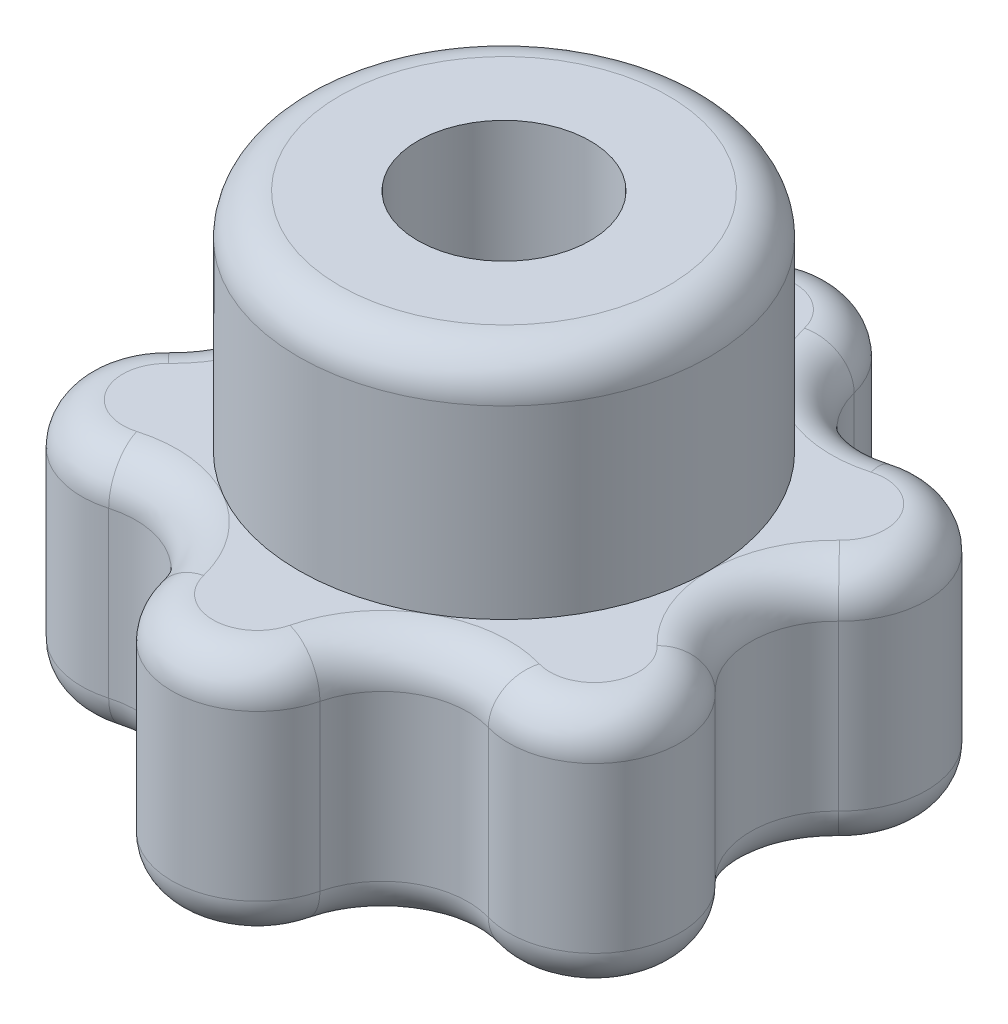
SolidWorks part; units mm, degrees
ref_plane "Спереди" through (0, 0, 0) normal (0, 0, 1) x (1, 0, 0)
ref_plane "Сверху" through (0, 0, 0) normal (0, 1, 0) x (1, 0, 0)
ref_plane "Справа" through (0, 0, 0) normal (1, 0, 0) x (0, 0, -1)
sketch "Эскиз1" plane through (0, 0, 0) normal (0, 1, 0) x (1, 0, 0)
  line L1 (0, 4.2147) -> (-3.65, 2.1073)
  line L2 (-3.65, 2.1073) -> (-3.65, -2.1073)
  line L3 (-3.65, -2.1073) -> (0, -4.2147)
  line L4 (0, -4.2147) -> (3.65, -2.1073)
  line L5 (3.65, -2.1073) -> (3.65, 2.1073)
  line L6 (3.65, 2.1073) -> (0, 4.2147)
  circle A0 centre (0, 0) radius 6 construction
  arc A1 (2.0203, 6.4992) -> (-2.0203, 6.4992) centre (0, 6) ccw
  arc A2 (2.0203, 6.4992) -> (4.6183, 4.9992) centre (4.0405, 6.9984) ccw
  arc A3 (-2.0203, -6.4992) -> (2.0203, -6.4992) centre (0, -6) ccw
  arc A4 (4.6183, -4.9992) -> (2.0203, -6.4992) centre (4.0405, -6.9984) ccw
  arc A5 (6.6386, 1.5) -> (4.6183, 4.9992) centre (5.1962, 3) ccw
  arc A6 (6.6386, 1.5) -> (6.6386, -1.5) centre (8.081, 0) ccw
  arc A7 (4.6183, -4.9992) -> (6.6386, -1.5) centre (5.1962, -3) ccw
  arc A8 (-4.6183, 4.9992) -> (-2.0203, 6.4992) centre (-4.0405, 6.9984) ccw
  arc A9 (-4.6183, 4.9992) -> (-6.6386, 1.5) centre (-5.1962, 3) ccw
  arc A10 (-6.6386, -1.5) -> (-6.6386, 1.5) centre (-8.081, 0) ccw
  arc A11 (-2.0203, -6.4992) -> (-4.6183, -4.9992) centre (-4.0405, -6.9984) ccw
  arc A12 (-6.6386, -1.5) -> (-4.6183, -4.9992) centre (-5.1962, -3) ccw
  circle A13 centre (0, 0) radius 3.65 construction
  point P6 (0, 0)
  dimension "D1" = 12
  dimension "D2" = 7.3
extrude "Бобышка-Вытянуть1" add sketch "Эскиз1" along normal blind 6 contours A7 A6 A5 A2 A1 A8 A9 A10 A12 A11 A3 A4
sketch "Эскиз2" plane through (0, 6, 0) normal (0, 1, 0) x (1, 0, 0)
  circle A0 centre (0, 0) radius 5
  dimension "D1" = 10
extrude "Бобышка-Вытянуть2" add sketch "Эскиз2" along normal blind 5.5
sketch "Эскиз3" plane through (0, 11.5, 0) normal (0, 1, 0) x (1, 0, 0)
  circle A0 centre (0, 0) radius 2.1
  dimension "D1" = 4.2
extrude "Вырез-Вытянуть1" cut sketch "Эскиз3" against normal through all
extrude "Вырез-Вытянуть2" cut sketch "Эскиз1<3>" along normal blind 3 contours L1 L2 L3 L4 L5 L6
sketch "Эскиз1<3>" plane through (0, 0, 0) normal (0, 1, 0) x (1, 0, 0) same geometry as "Эскиз1"
fillet "Скругление1" radius 1 25 edges at (-3, 6, 5.1962) (-6.9984, 6, 4.0405) (-6, 6, 0) (-6.9984, 6, -4.0405) (-3, 6, -5.1962) (0, 6, -8.081) (3, 6, -5.1962) (6.9984, 6, -4.0405) (6, 6, 0) (6.9984, 6, 4.0405) (3, 6, 5.1962) (-3, 0, 5.1962) (-6.9984, 0, 4.0405) (-6, 0, 0) (-6.9984, 0, -4.0405) (-3, 0, -5.1962) (0, 0, -8.081) (3, 0, -5.1962) (6.9984, 0, -4.0405) (6, 0, 0) (6.9984, 0, 4.0405) (3, 0, 5.1962) (0, 11.5, 5) (0, 6, 8.081) (0, 0, 8.081)
